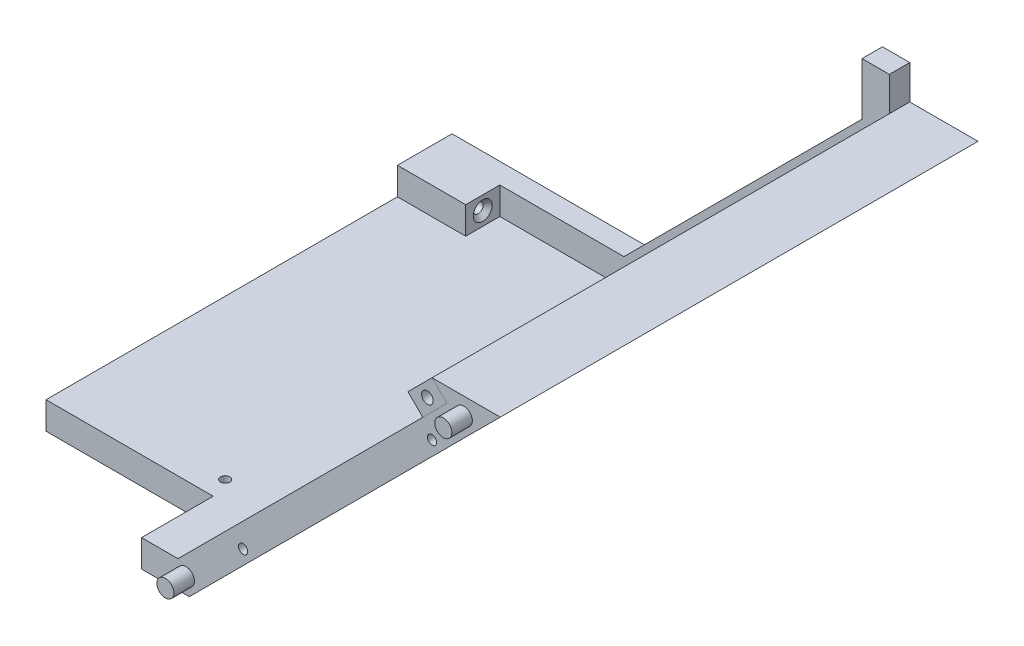
SolidWorks part; units mm, degrees
ref_plane "Plan de face" through (0, 0, 0) normal (0, 0, 1) x (1, 0, 0)
ref_plane "Plan de dessus" through (0, 0, 0) normal (0, 1, 0) x (1, 0, 0)
ref_plane "Plan de droite" through (0, 0, 0) normal (1, 0, 0) x (0, 0, -1)
sketch "Main-Sketch" plane through (0, 0, 0) normal (0, 0, 1) x (1, 0, 0)
  line L0 (0, 0) -> (63, 0)
  line L1 (63, 0) -> (154.15, 91.15)
  line L2 (154.15, 91.15) -> (134.15, 91.15)
  line L3 (134.15, 91.15) -> (138.4931, 86.8069)
  line L4 (138.4931, 86.8069) -> (59.6863, 8)
  line L5 (59.6863, 8) -> (0, 8)
  line L6 (0, 8) -> (0, 0)
  dimension "D1" = 8
  dimension "D2" = 8
  dimension "D3" = 20
  dimension "D4" = 135
  dimension "D5" = 154.15
  dimension "D6" = 63
extrude "Main-Extrusion" add sketch "Main-Sketch" along normal blind 140
sketch "Lcd-Hole-Sketch" plane through (0, 8, 0) normal (0, 1, 0) x (-1, 0, 0)
  line L1 (0, 140) -> (-49, 140)
  line L2 (0, 140) -> (0, 119)
  line L3 (0, 119) -> (-49, 119)
  line L4 (-49, 140) -> (-49, 119)
  dimension "D1" = 21
  dimension "D2" = 49
extrude "Lcd-Hole" cut sketch "Lcd-Hole-Sketch" against normal through all
sketch "Lcd-Fix-Sketch" plane through (0, 8, 0) normal (0, 1, 0) x (1, 0, 0)
  line L1 (49, -119) -> (0, -119) construction
  line L2 (49, -140) -> (49, -119) construction
  circle A0 centre (46.5, -113) radius 1.35
  dimension "D1" = 2.7
  dimension "D2" = 2.5
  dimension "D3" = 6
extrude "Lcd-Fix" cut sketch "Lcd-Fix-Sketch" against normal blind 7
sketch "Bottom-Fix-Sketch" plane through (0, 0, 0) normal (0, 0, 1) x (1, 0, 0)
  line L0 (59.6863, 8) -> (138.4931, 86.8069)
  line L1 (134.15, 101.15) -> (126.15, 101.15)
  line L2 (126.15, 101.15) -> (126.15, 85.7774)
  line L5 (138.4931, 86.8069) -> (59.6863, 8) construction
  line L6 (134.15, 91.15) -> (134.15, 101.15)
  line L7 (59.6863, 8) -> (0, 8)
  line L8 (0, 0) -> (0, 8) construction
  line L9 (0, 8) -> (0, 16)
  line L10 (0, 16) -> (56.3726, 16)
  line L11 (56.3726, 16) -> (126.15, 85.7774)
  line L13 (138.4931, 86.8069) -> (134.15, 91.15)
  dimension "D1" = 8
  dimension "D2" = 10
  dimension "D3" = 8
  dimension "D4" = 8
extrude "Bottom-Fix" add sketch "Bottom-Fix-Sketch" along normal blind 6 separate body
sketch "Power-Board-Hole-Sketch" plane through (22.4244, -40.5756, 188.8128) normal (0.7071, -0.7071, 0) x (0, 0, -1)
  line L1 (150.8128, 154.2882) -> (68.8128, 154.2882)
  line L2 (150.8128, 154.2882) -> (150.8128, 80.3826)
  line L3 (150.8128, 80.3826) -> (68.8128, 80.3826)
  line L4 (68.8128, 154.2882) -> (68.8128, 80.3826)
  line L6 (188.8128, 57.3826) -> (188.8128, 186.2882) construction
  line L7 (48.8128, 57.3826) -> (48.8128, 186.2882) construction
  line L8 (48.8128, 57.3826) -> (188.8128, 57.3826) construction
  line L9 (48.8128, 186.2882) -> (188.8128, 186.2882) construction
  dimension "D1" = 20
  dimension "D2" = 38
  dimension "D3" = 32
  dimension "D4" = 23
extrude "Power-Board-Hole" cut sketch "Power-Board-Hole-Sketch" against normal through all
sketch "Power-Board-Window-Sketch" plane through (22.4244, -40.5756, 188.8128) normal (0.7071, -0.7071, 0) x (0, 0, -1)
  line L0 (150.8128, 80.3826) -> (150.8128, 154.2882) construction
  line L1 (156.8128, 160.2882) -> (62.8128, 160.2882)
  line L2 (156.8128, 160.2882) -> (156.8128, 74.3826)
  line L3 (156.8128, 74.3826) -> (62.8128, 74.3826)
  line L4 (62.8128, 160.2882) -> (62.8128, 74.3826)
  line L5 (150.8128, 154.2882) -> (68.8128, 154.2882) construction
  line L6 (68.8128, 154.2882) -> (68.8128, 80.3826) construction
  line L7 (68.8128, 80.3826) -> (150.8128, 80.3826) construction
  dimension "D1" = 6
  dimension "D2" = 6
  dimension "D3" = 6
  dimension "D4" = 6
extrude "Power-Board-Window" cut sketch "Power-Board-Window-Sketch" against normal blind 5
sketch " Power-Board-Window-Fix-Sketch" plane through (27.9645, -27.9645, 0) normal (0.7071, -0.7071, 0) x (0, 0, -1)
  line L0 (-38, 67.5477) -> (-38, 141.4533) construction
  line L1 (-38, 141.4533) -> (-120, 141.4533) construction
  line L2 (-120, 67.5477) -> (-38, 67.5477) construction
  line L3 (-120, 141.4533) -> (-120, 67.5477) construction
  circle A0 centre (-123, 104.5005) radius 1.35
  circle A1 centre (-35, 104.5005) radius 1.35
  circle A2 centre (-79, 144.4533) radius 1.35
  circle A3 centre (-79, 64.5477) radius 1.35
  point P11 (-38, 104.5005)
  point P15 (-79, 141.4533)
  point P19 (-79, 67.5477)
  point P22 (-120, 104.5005)
  dimension "D1" = 2.7
  dimension "D2" = 3
  dimension "D3" = 3
  dimension "D4" = 3
  dimension "D5" = 3
extrude "Power-Board-Window-Fix" cut sketch " Power-Board-Window-Fix-Sketch" against normal through all
sketch "PowerBoard-Fix-Sketch" plane through (25.8431, -25.8431, 0) normal (-0.7071, 0.7071, 0) x (0, 0, 1)
  line L0 (140, 159.3112) -> (0, 159.3112) construction
  line L2 (6, 47.8614) -> (6, 159.3112) construction
  circle A0 centre (13, 137.3112) radius 4
  circle A1 centre (11, 68.3112) radius 4
  dimension "D1" = 8
  dimension "D2" = 8
  dimension "D3" = 22
  dimension "D4" = 69
  dimension "D5" = 7
  dimension "D6" = 5
extrude "PowerBoard-Fix-Extrusion" add sketch "PowerBoard-Fix-Sketch" along normal blind 5
sketch "PowerBoard-Fix-Hole-Sketch" plane through (22.3076, -22.3076, 0) normal (-0.7071, 0.7071, 0) x (0, 0, 1)
  circle A0 centre (13, 137.3112) radius 1.35
  circle A1 centre (11, 68.3112) radius 1.35
  dimension "D1" = 2.7
extrude "PowerBoard-Fix-Hole" cut sketch "PowerBoard-Fix-Hole-Sketch" against normal through all
sketch "Top-Fix-Sketch" plane through (0, 0, 140) normal (0, 0, 1) x (1, 0, 0)
  line L0 (63, 0) -> (154.15, 91.15) construction
  line L1 (49, 0) -> (49, 8) construction
  line L2 (134.15, 91.15) -> (138.4931, 86.8069) construction
  circle A0 centre (62, 4.6569) radius 2.5
  circle A1 centre (143.4462, 86.0965) radius 2.5
  point P12 (49, 4)
  dimension "D1" = 5
  dimension "D2" = 5
  dimension "D4" = 4
  dimension "D5" = 3.9954
  dimension "D6" = 13
  dimension "D7" = 3
extrude "Top-Fix" add sketch "Top-Fix-Sketch" along normal blind 6
sketch "Top-Fix-Hole-Sketch" plane through (0, 0, 140) normal (0, 0, 1) x (1, 0, 0)
  line L0 (63, 0) -> (154.15, 91.15) construction
  circle A0 centre (78.7574, 20) radius 1.35
  circle A1 centre (134.15, 75.3926) radius 1.35
  dimension "D1" = 2.7
  dimension "D2" = 2.7
  dimension "D3" = 3
  dimension "D4" = 3
  dimension "D5" = 20
  dimension "D6" = 20
extrude "Top-Fix-Hole" cut sketch "Top-Fix-Hole-Sketch" against normal blind 30
sketch "Esquisse3" plane through (0, 0, 140) normal (0, 0, 1) x (1, 0, 0)
  line L0 (138.4931, 86.8069) -> (134.15, 91.15)
  line L1 (134.15, 91.15) -> (127.0789, 84.0789)
  line L2 (127.0789, 84.0789) -> (131.4221, 79.7358)
  line L3 (138.4931, 86.8069) -> (59.6863, 8) construction
  line L4 (131.4221, 79.7358) -> (138.4931, 86.8069)
  dimension "D1" = 10
extrude "Boss.-Extru.2" add sketch "Esquisse3" against normal blind 10 separate body
hole_wizard "Fraisage pour vis à tête fraisée M31" positions "Esquisse5" profile "Esquisse4" countersink size "M3" standard "Ansi Metric" end condition up to next
sketch "Esquisse5" plane through (0, 0, 130) normal (0, 0, -1) x (-1, 0, 0)
  line L0 (-127.0789, 84.0789) -> (-131.4221, 79.7358) construction
  line L1 (-134.15, 91.15) -> (-127.0789, 84.0789) construction
  point P0 (-132.7853, 85.4436)
  dimension "D1" = 5
  dimension "D2" = 3.07
sketch "Esquisse4" plane through (132.7853, 85.4436, 130) normal (1, 0, 0) x (0, 1, 0)
  line L0 (0, 0) -> (0, 10.001)
  line L1 (0, 10.001) -> (1.7, 10.001)
  line L2 (1.7, 10.001) -> (1.7, 1.3)
  line L3 (1.7, 1.3) -> (3, 0)
  line L5 (3, 0) -> (0, 0)
  line L6 (-1.7, 1.3) -> (-3, 0) construction
  line L11 (0, -6.35) -> (0, 107.95) construction
  dimension "Diamètre du perçage jusqu'au prochain" = 3.4
  dimension "Profondeur du perçage jusqu'au prochain" = 10.001
  dimension "Diamètre du fraisage entrant" = 6
  dimension "Angle du fraisage entrant" = 90
sketch "Fix6Sketch" plane through (0, 0, 0) normal (-1, 0, 0) x (0, 0, 1)
  line L0 (119, 0) -> (119, 8) construction
  circle A0 centre (104, 4) radius 2.5
  circle A1 centre (74, 4) radius 2.5
  circle A2 centre (44, 4) radius 2.5
  circle A3 centre (14, 4) radius 2.5
  point P10 (119, 4)
  dimension "D2" = 5
  dimension "D1" = 15
  dimension "D3" = 30
  dimension "D4" = 30
  dimension "D5" = 30
extrude "Fix-Hole" cut sketch "Fix6Sketch" against normal blind 10
ref_plane "EndOfFix-Plan" through (15, 0, 0) normal (-1, 0, 0) x (0, 0, 1)
ref_axis "EndOfFix-Axe" through (15, -0.8, 6) along (0, 1, 0)
ref_plane "EndOFix-Inclined-Plan" through (15.4952, 0, 4.1519) normal (-0.9659, 0, -0.2588) x (0, 1, 0)
sketch "Esquisse6" plane through (0, 0, 0) normal (-1, 0, 0) x (0, 0, 1)
  line L0 (0, 12.5) -> (6, 11.5)
  line L1 (6, 16) -> (6, 8) construction
  line L2 (6, 11.5) -> (6, 3.5)
  line L3 (6, 3.5) -> (0, 2.5)
  line L4 (0, 8) -> (0, 0) construction
  line L5 (0, 2.5) -> (0, 12.5)
  line L8 (0, 16) -> (0, 8) construction
  point P2 (6, 9.9632)
  point P4 (0, 5)
  point P12 (6, 7.5)
  point P13 (0, 7.5)
  point P14 (6, 3.4672)
  point P15 (0, 0)
  dimension "D1" = 2.5
  dimension "D2" = 8
  dimension "D3" = 10
extrude "Enlèv. mat.-Extru.1" cut sketch "Esquisse6" against normal up to surface (16.6077 mm away) up to plane "EndOFix-Inclined-Plan"
sketch "Esquisse8" plane through (0, 8, 0) normal (0, 1, 0) x (1, 0, 0)
  line L0 (15, -6) -> (59.6863, -6) construction
  line L1 (0, -16) -> (20, -16)
  line L2 (0, -16) -> (0, -6)
  line L3 (0, -6) -> (20, -6)
  line L4 (20, -16) -> (20, -6)
  line L5 (0, -119) -> (0, -6) construction
  point P6 (0.3386, -15.2667)
  point P7 (0, -14.9483)
  dimension "D1" = 20
  dimension "D2" = 10
extrude "Boss.-Extru.3" add sketch "Esquisse8" along normal up to surface (8 mm away) up to face at (28.1863, 16, 3)
hole_wizard "Fraisage pour vis à tête fraisée M2.51" positions "Esquisse10" profile "Esquisse9" countersink size "M2.5" standard "Ansi Metric" end condition through all
sketch "Esquisse10" plane through (20, 0, 0) normal (1, 0, 0) x (0, 0, -1)
  line L0 (-16, 16) -> (-16, 8) construction
  line L2 (-6, 16) -> (-16, 16) construction
  point P0 (-11, 12)
  point P1 (0, 0)
  point P4 (-16, 12)
  point P9 (0, 0)
  point P10 (-11, 16)
sketch "Esquisse9" plane through (20, 12, 11) normal (0, 1, 0) x (0, 0, -1)
  line L0 (0, 0) -> (0, 20)
  line L1 (0, 20) -> (1.45, 20)
  line L2 (1.45, 20) -> (1.45, 1.3)
  line L3 (1.45, 1.3) -> (2.75, 0)
  line L5 (2.75, 0) -> (0, 0)
  line L6 (-1.45, 1.3) -> (-2.75, 0) construction
  line L11 (0, -6.35) -> (0, 107.95) construction
  dimension "Diamètre du perçage jusqu'au prochain" = 2.9
  dimension "Profondeur du perçage jusqu'au prochain" = 20
  dimension "Diamètre du fraisage entrant" = 5.5
  dimension "Angle du fraisage entrant" = 90
